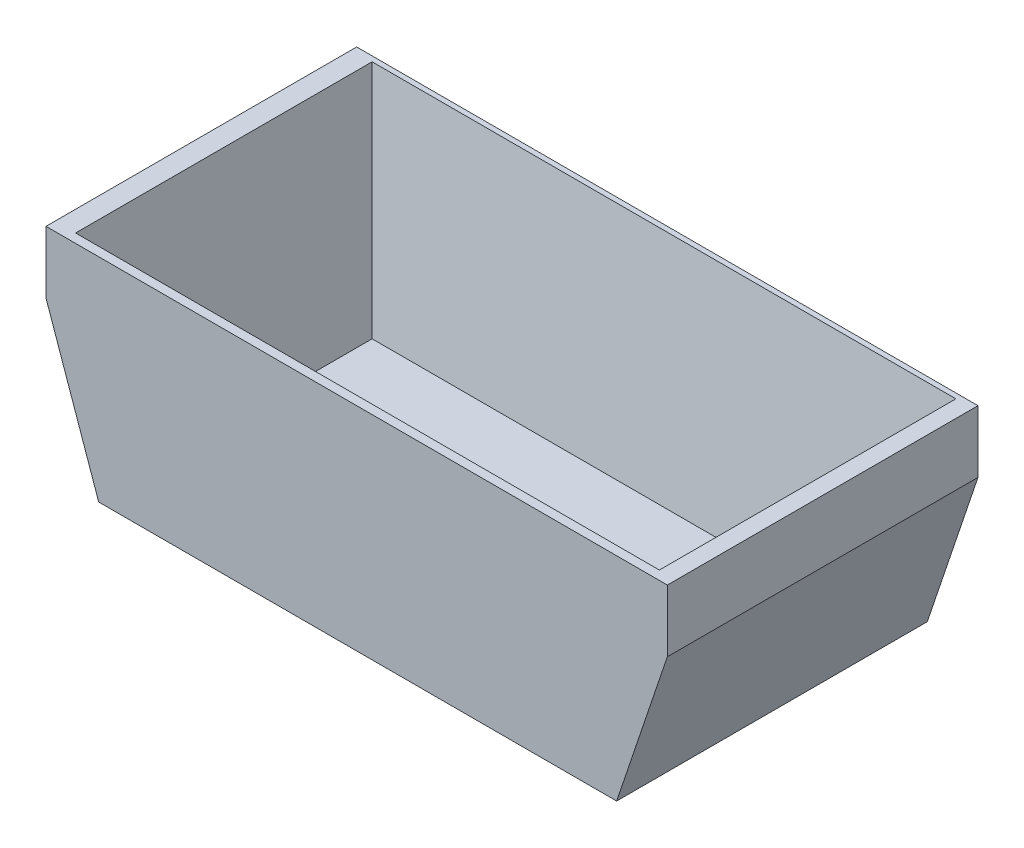
SolidWorks part; units mm, degrees
ref_plane "Front Plane" through (0, 0, 0) normal (0, 0, 1) x (1, 0, 0)
ref_plane "Top Plane" through (0, 0, 0) normal (0, 1, 0) x (1, 0, 0)
ref_plane "Right Plane" through (0, 0, 0) normal (1, 0, 0) x (0, 0, -1)
sketch "Sketch1" plane through (0, 0, 0) normal (0, 0, 1) x (1, 0, 0)
  line L0 (-49.7914, 32.6453) -> (-19.7914, 32.6453)
  line L1 (-19.7914, 32.6453) -> (-19.7914, 29.6453)
  line L2 (-49.7914, 32.6453) -> (-49.7914, 29.6453)
  line L6 (-47.2477, 22.3886) -> (-22.239, 22.3886)
  line L8 (-49.7914, 29.6453) -> (-47.2477, 22.3886)
  line L9 (-19.7914, 29.6453) -> (-22.239, 22.3886)
extrude "Boss-Extrude1" add sketch "Sketch1" along normal blind 15
sketch "Sketch2" plane through (0, 32.6453, 0) normal (0, 1, 0) x (1, 0, 0)
sketch "Sketch3" plane through (0, 32.6453, 0) normal (0, 1, 0) x (1, 0, 0)
  line L1 (-49.7914, 0) -> (-19.7914, 0)
  line L2 (-49.7914, 0) -> (-49.7914, -15)
  line L3 (-49.7914, -15) -> (-19.7914, -15)
  line L4 (-19.7914, 0) -> (-19.7914, -15)
sketch "Sketch4" plane through (0, 32.6453, 0) normal (0, 1, 0) x (1, 0, 0)
  line L1 (-48.7975, -0.248) -> (-20.6113, -0.248)
  line L2 (-48.7975, -0.248) -> (-48.7975, -14.5652)
  line L3 (-48.7975, -14.5652) -> (-20.6113, -14.5652)
  line L4 (-20.6113, -0.248) -> (-20.6113, -14.5652)
extrude "Cut-Extrude2" cut sketch "Sketch4" against normal blind 10 draft 9
sketch "Sketch5" plane through (0, 0, 15) normal (0, 0, 1) x (1, 0, 0)
  circle A0 centre (-43.9573, 24.0758) radius 0.129
scale "Scale4" bodies to scale 103 scale about centroid uniform scaling yes scale factor 10
sketch "Sketch6" plane through (0, 0, 79.4894) normal (0, 0, 1) x (1, 0, 0)
  line L0 (-160.7169, -6.7592) -> (96.2484, -6.7592)
  line L1 (-182.6485, 55.8085) -> (-157.2117, -16.7592) construction
  line L2 (92.8756, -16.7592) -> (117.3515, 55.8085) construction
  line L3 (-157.2117, -16.7592) -> (92.8756, -16.7592) construction
  circle A0 centre (-118.6872, -6.7592) radius 1.8
  dimension "D2" = 3.6
  dimension "D1" = 10
